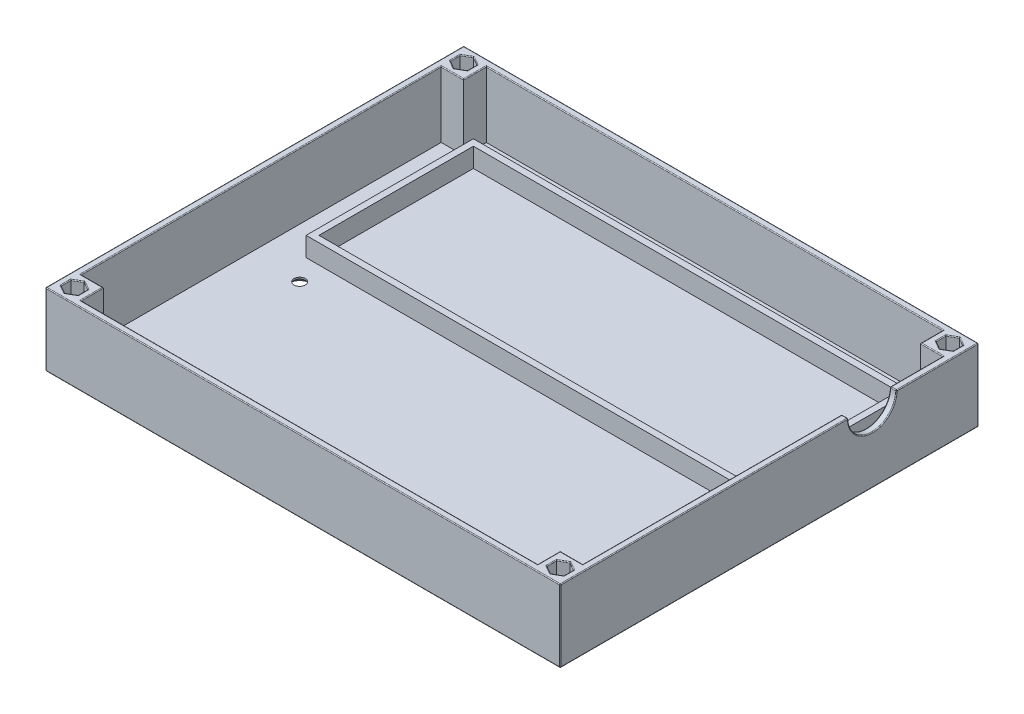
SolidWorks part; units mm, degrees
ref_plane "Front Plane" through (0, 0, 0) normal (0, 0, 1) x (1, 0, 0)
ref_plane "Top Plane" through (0, 0, 0) normal (0, 1, 0) x (1, 0, 0)
ref_plane "Right Plane" through (0, 0, 0) normal (1, 0, 0) x (0, 0, -1)
sketch "Sketch1" plane through (0, 0, 0) normal (0, 1, 0) x (1, 0, 0)
  line L0 (-80, 26) -> (-71, 26)
  line L5 (-68, 26) -> (68, 26)
  line L6 (-66, -24) -> (66, -24)
  line L7 (-80, 35) -> (80, 35)
  line L8 (-80, 35) -> (-80, -95)
  line L9 (-80, -95) -> (80, -95)
  line L10 (80, 35) -> (80, -95)
  line L11 (-71, 26) -> (-71, 35)
  line L12 (-80, -86) -> (-71, -86)
  line L13 (-71, -86) -> (-71, -95)
  line L14 (71, -95) -> (71, -86)
  line L15 (71, -86) -> (80, -86)
  line L16 (80, 26) -> (71, 26)
  line L17 (71, 26) -> (71, 35)
  line L18 (0, -33.5) -> (0, -26) construction
  line L19 (-71, 26) -> (-80, 35) construction
  line L20 (71, 26) -> (80, 35) construction
  line L21 (-71, -86) -> (-80, -95) construction
  line L22 (71, -86) -> (80, -95) construction
  line L23 (-66, -24) -> (-66, 24)
  line L24 (-66, 24) -> (66, 24)
  line L25 (66, -24) -> (66, 24)
  line L34 (78, -86) -> (78, 26)
  line L35 (-80, -95) -> (80, -95) construction
  line L36 (-80, -95) -> (-80, 26) construction
  line L38 (80, -95) -> (80, -34) construction
  line L39 (71, 33) -> (-71, 33)
  line L40 (-78, 26) -> (-78, -86)
  line L41 (-71, -93) -> (71, -93)
  line L42 (0, 24) -> (0, -24) construction
  line L43 (-66, 0) -> (66, 0) construction
  line L44 (-71, -86) -> (71, -86) construction
  line L45 (-62.5, -78.5) -> (62.5, -78.5) construction
  line L46 (-62.5, -78.5) -> (-62.5, -33.5) construction
  line L47 (-62.5, -33.5) -> (62.5, -33.5) construction
  line L48 (62.5, -78.5) -> (62.5, -33.5) construction
  line L49 (0, -33.5) -> (0, -78.5) construction
  line L50 (-62.5, -56) -> (62.5, -56) construction
  line L51 (0, -78.5) -> (0, -86) construction
  line L52 (68, -26) -> (68, 26)
  line L53 (-68, -26) -> (68, -26)
  line L54 (-68, -26) -> (-68, 26)
  line L55 (-68, 26) -> (-71, 26) construction
  circle A0 centre (-75.5, 30.5) radius 1.75
  circle A1 centre (75.5, 30.5) radius 1.75
  circle A2 centre (75.5, -90.5) radius 1.75
  circle A3 centre (-75.5, -90.5) radius 1.75
  circle A4 centre (-62.5, -33.5) radius 1.75
  circle A5 centre (-62.5, -78.5) radius 1.75
  circle A6 centre (62.5, -78.5) radius 1.75
  circle A7 centre (62.5, -33.5) radius 1.75
  point P0 (0, 0)
  point P2 (0, 0)
  point P56 (0, -56)
  dimension "D1" = 9
  dimension "D3" = 3.5
  dimension "D5" = 132
  dimension "D11" = 3.5
  dimension "D2" = 121
  dimension "D4" = 160
  dimension "D6" = 48
  dimension "D7" = 2
  dimension "D8" = 2
  dimension "D9" = 45
  dimension "D12" = 2
  dimension "D13" = 2
  dimension "D14" = 2
  dimension "D15" = 125
extrude "Boss-Extrude1" add sketch "Sketch1" against normal blind 2 contours L16 L17 L7 L11 L0 L8 L12 L13 L9 L14 L15 L10 | L15 L14 L9 L10 A2 | L17 L16 L10 L7 A1 | L13 L12 L8 L9 A3 | L0 L11 L7 L8 A0 | L40 L34 L16 L17 L39 L11 L0 | L34 L10 L16 | L39 L17 L7 L11 | L8 L40 L0 | L17 L39 L11 | L17 L11 | L16 L0 | L41 L13 L9 L14 | A7 L47 A4 L46 A5 L45 A6 L48 | L6 L25 L24 L23 | L54 L53 L52 L5 L25 L6 L23 L24 region at (-79.8727, 0, -30.5) region at (-79, 0, 30) region at (0, 0, 47.0986) region at (-79, 0, 86.1273) region at (0, 0, -34) region at (75.5, 0, -34.8727) region at (0, 0, 94) region at (71.1273, 0, 94) region at (79, 0, 30) region at (0, 0, -24.544) region at (0, 0, 0)
extrude "Boss-Extrude3" add sketch "Sketch1<4>" along normal blind 20.5 contours L8 L40 L0 | L34 L10 L16 | L39 L17 L7 L11 | L17 L16 L10 L7 A1 | L0 L11 L7 L8 A0 | L13 L12 L8 L9 A3 | L41 L13 L9 L14 | L15 L14 L9 L10 A2 region at (-79.8727, 0, -30.5) region at (-79, 0, 30) region at (-79, 0, 86.1273) region at (0, 0, -34) region at (75.5, 0, -34.8727) region at (0, 0, 94) region at (71.1273, 0, 94) region at (79, 0, 30)
sketch "Sketch1<4>" plane through (0, 0, 0) normal (0, 1, 0) x (1, 0, 0) same geometry as "Sketch1"
extrude "Boss-Extrude5" add sketch "Sketch1<6>" along normal blind 6 contours L54 L53 L52 L5 L25 L6 L23 L24 region at (0, 0, -24.544)
sketch "Sketch1<6>" plane through (0, 0, 0) normal (0, 1, 0) x (1, 0, 0) same geometry as "Sketch1"
sketch "Sketch2" plane through (80, 0, 0) normal (1, 0, 0) x (0, 0, -1)
  line L0 (2, -2) -> (2, 20.5) construction
  line L1 (35, -2) -> (-95, -2) construction
  line L2 (35, 20.5) -> (-95, 20.5) construction
  line L3 (2, 20.5) -> (35, 20.5) construction
  circle A0 centre (2, 20.5) radius 7.5
  dimension "D2" = 15
  dimension "D1" = 33
extrude "Cut-Extrude1" cut sketch "Sketch2" against normal blind 2
ref_plane "Plane1" through (0, 20.5, 0) normal (0, -1, 0) x (-1, 0, 0)
chamfer "Chamfer1" distance 1.5 angle 45 8 edges at (-75.5, -2, -28.75) (-62.5, -2, 80.25) (-62.5, -2, 35.25) (-75.5, -2, 92.25) (75.5, -2, 92.25) (62.5, -2, 80.25) (62.5, -2, 35.25) (75.5, -2, -28.75)
sketch "Sketch4" plane through (0, 20.5, 0) normal (0, -1, 0) x (-1, 0, 0)
  line L0 (75.5, -90.5) -> (75.5, -87.4689) construction
  line L1 (75.5, -93.5311) -> (78.125, -92.0155)
  line L2 (78.125, -92.0155) -> (78.125, -88.9845)
  line L3 (78.125, -88.9845) -> (75.5, -87.4689)
  line L4 (75.5, -87.4689) -> (72.875, -88.9845)
  line L5 (72.875, -88.9845) -> (72.875, -92.0155)
  line L6 (72.875, -92.0155) -> (75.5, -93.5311)
  line L7 (-75.5, -87.4689) -> (-78.125, -88.9845)
  line L8 (-78.125, -88.9845) -> (-78.125, -92.0155)
  line L9 (-78.125, -92.0155) -> (-75.5, -93.5311)
  line L10 (-75.5, -93.5311) -> (-72.875, -92.0155)
  line L11 (-72.875, -92.0155) -> (-72.875, -88.9845)
  line L12 (-72.875, -88.9845) -> (-75.5, -87.4689)
  line L13 (-75.5, 27.4689) -> (-72.875, 28.9845)
  line L14 (-72.875, 28.9845) -> (-72.875, 32.0155)
  line L15 (-72.875, 32.0155) -> (-75.5, 33.5311)
  line L16 (-75.5, 33.5311) -> (-78.125, 32.0155)
  line L17 (-78.125, 32.0155) -> (-78.125, 28.9845)
  line L18 (-78.125, 28.9845) -> (-75.5, 27.4689)
  line L19 (75.5, 33.5311) -> (72.875, 32.0155)
  line L20 (72.875, 32.0155) -> (72.875, 28.9845)
  line L21 (72.875, 28.9845) -> (75.5, 27.4689)
  line L22 (75.5, 27.4689) -> (78.125, 28.9845)
  line L23 (78.125, 28.9845) -> (78.125, 32.0155)
  line L24 (78.125, 32.0155) -> (75.5, 33.5311)
  line L25 (-75.5, -90.5) -> (-75.5, -87.4689) construction
  line L26 (-75.5, 30.5) -> (-75.5, 33.5311) construction
  line L27 (75.5, 30.5) -> (75.5, 33.5311) construction
  circle A0 centre (75.5, -90.5) radius 2.625 construction
  circle A1 centre (-75.5, -90.5) radius 2.625 construction
  circle A2 centre (-75.5, 30.5) radius 2.625 construction
  circle A3 centre (75.5, 30.5) radius 2.625 construction
  dimension "D1" = 5.25
extrude "Cut-Extrude2" cut sketch "Sketch4" along normal blind 5.25
fillet "Fillet1" radius 0.25 62 edges at (-80, -2, 30) (0, -2, 95) (80, -2, 30) (0, -2, -35) (78, 13, -2) (80, 13, -2) (80, 20.5, 50.25) (0, 20.5, 95) (-80, 20.5, 30) (0, 20.5, -35) (80, 20.5, -22.25) (79, 20.5, -9.5) (78, 20.5, -17.75) (74.5, 20.5, -26) (71, 20.5, -29.5) (0, 20.5, -33) (-71, 20.5, -29.5) (-78, 20.5, 30) (-74.5, 20.5, 86) (-71, 20.5, 89.5) (0, 20.5, 93) (71, 20.5, 89.5) (74.5, 20.5, 86) (78, 20.5, 45.75) (79, 20.5, 5.5) (80, 9.25, 95) (80, 9.25, -35) (-80, 9.25, -35) (-80, 9.25, 95) (75.5, -2, -27.25) (62.5, -2, 36.75) (62.5, -2, 81.75) (75.5, -2, 93.75) (-75.5, -2, 93.75) (-62.5, -2, 36.75) (-62.5, -2, 81.75) (-75.5, -2, -27.25) (-76.8125, 20.5, -28.2267) (-74.1875, 20.5, -28.2267) (-72.875, 20.5, -30.5) (-74.1875, 20.5, -32.7733) (-76.8125, 20.5, -32.7733) (-78.125, 20.5, -30.5) (74.1875, 20.5, 92.7733) (76.8125, 20.5, 92.7733) (78.125, 20.5, 90.5) (76.8125, 20.5, 88.2267) (74.1875, 20.5, 88.2267) (72.875, 20.5, 90.5) (-74.1875, 20.5, 88.2267) (-76.8125, 20.5, 88.2267) (-78.125, 20.5, 90.5) (-76.8125, 20.5, 92.7733) (-74.1875, 20.5, 92.7733) (-72.875, 20.5, 90.5) (76.8125, 20.5, -32.7733) (74.1875, 20.5, -32.7733) (72.875, 20.5, -30.5) (74.1875, 20.5, -28.2267) (76.8125, 20.5, -28.2267) (78.125, 20.5, -30.5) (-74.5, 20.5, -26)
